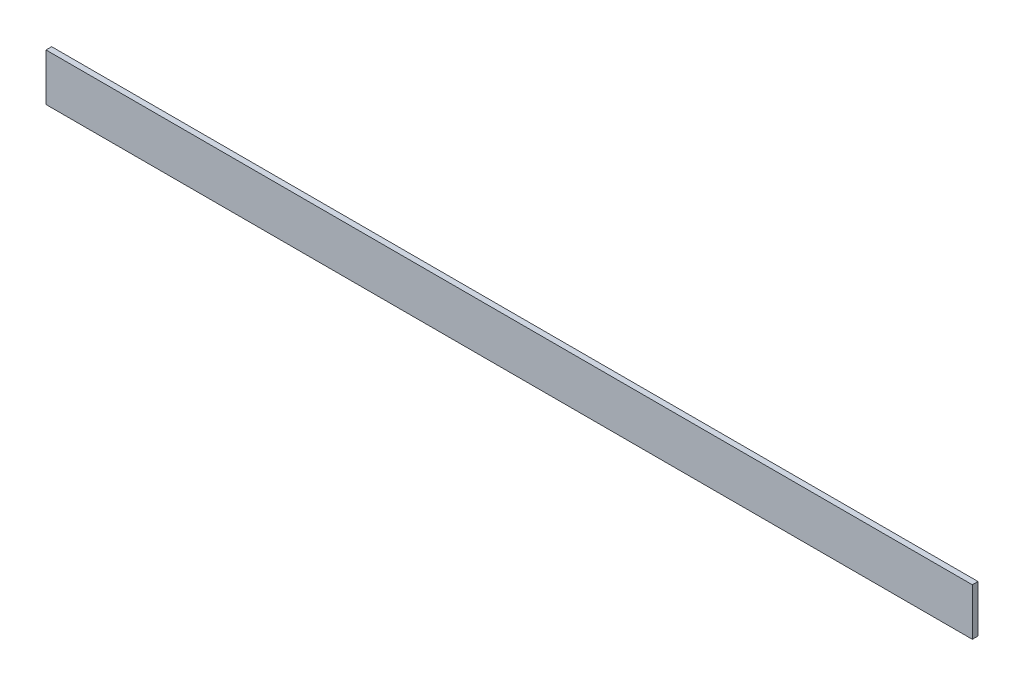
SolidWorks part; units mm, degrees
ref_plane "Спереди" through (0, 0, 0) normal (0, 0, 1) x (1, 0, 0)
ref_plane "Сверху" through (0, 0, 0) normal (0, 1, 0) x (1, 0, 0)
ref_plane "Справа" through (0, 0, 0) normal (1, 0, 0) x (0, 0, -1)
sketch "Эскиз1" plane through (0, 0, 0) normal (1, 0, 0) x (0, 0, -1)
  line L0 (0, 0) -> (25, 0)
  line L1 (0, 0) -> (0, 25)
extrude "Вытянуть-Тонкостенный1" add sketch "Эскиз1" along normal blind 490 thin thin type one direction wall 3
sketch "Эскиз2" plane through (0, 0, 0) normal (0, -1, 0) x (1, 0, 0)
  line L0 (245, 0) -> (245, -44.4018) construction
  line L1 (0, -25) -> (22, -25)
  line L2 (0, -25) -> (0, -3)
  line L3 (0, -3) -> (22, -3)
  line L4 (22, -25) -> (22, -3)
  line L5 (490, 0) -> (0, 0) construction
  line L6 (468, -25) -> (468, -3)
  line L7 (490, -3) -> (468, -3)
  line L8 (490, -25) -> (490, -3)
  line L9 (490, -25) -> (468, -25)
extrude "Вырез-Вытянуть1" cut sketch "Эскиз2" against normal through all
